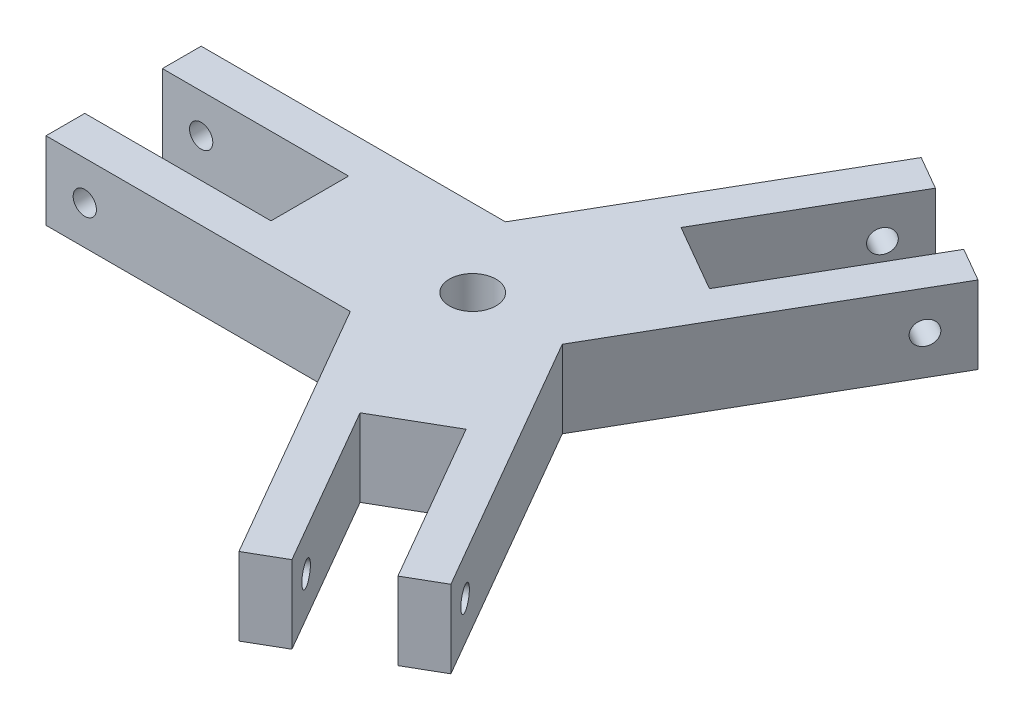
SolidWorks part; units mm, degrees
ref_plane "Front Plane" through (0, 0, 0) normal (0, 0, 1) x (1, 0, 0)
ref_plane "Top Plane" through (0, 0, 0) normal (0, 1, 0) x (1, 0, 0)
ref_plane "Right Plane" through (0, 0, 0) normal (1, 0, 0) x (0, 0, -1)
ref_axis "Axis1" through (0, -55, 0) along (0, 1, 0)
sketch "Sketch1" plane through (0, 0, 0) normal (0, 0, 1) x (1, 0, 0)
  line L1 (0, 0) -> (-45, 0)
  line L2 (0, 0) -> (0, 10)
  line L3 (0, 10) -> (-45, 10)
  line L4 (-45, 0) -> (-45, 10)
  dimension "D1" = 45
  dimension "D2" = 10
extrude "Main" add sketch "Sketch1" along normal mid plane 20
sketch "Sketch2" plane through (0, 0, 10) normal (0, 0, 1) x (1, 0, 0)
  line L0 (-45, 0) -> (0, 0) construction
  line L1 (0, -55) -> (0, 55) construction
  circle A0 centre (-40, 5) radius 1.5
  dimension "D3" = 3
  dimension "D1" = 5
  dimension "D2" = 40
extrude "Cut-Extrude1" cut sketch "Sketch2" against normal through all both and the other way through all
sketch "Sketch4" plane through (0, 10, 0) normal (0, 1, 0) x (1, 0, 0)
  line L0 (-45, -10) -> (-45, 10) construction
  line L1 (-21, 5) -> (-45, 5)
  line L2 (-21, 5) -> (-21, -5)
  line L3 (-21, -5) -> (-45, -5)
  line L4 (-45, 5) -> (-45, -5)
  line L5 (0, 10) -> (-45, 10) construction
  line L6 (0, -10) -> (-45, -10) construction
  dimension "D1" = 5
  dimension "D2" = 5
  dimension "D3" = 24
extrude "Cut-Extrude3" cut sketch "Sketch4" against normal through all
pattern_circular "CirPattern1" count 3 every 120 about axis through (0, -55, 0) along (0, 1, 0) of "Main", "Cut-Extrude1", "Cut-Extrude3"
sketch "Sketch3" plane through (0, 10, 0) normal (0, 1, 0) x (1, 0, 0)
  circle A0 centre (0, 0) radius 3
  dimension "D1" = 6
extrude "Cut-Extrude2" cut sketch "Sketch3" against normal through all
